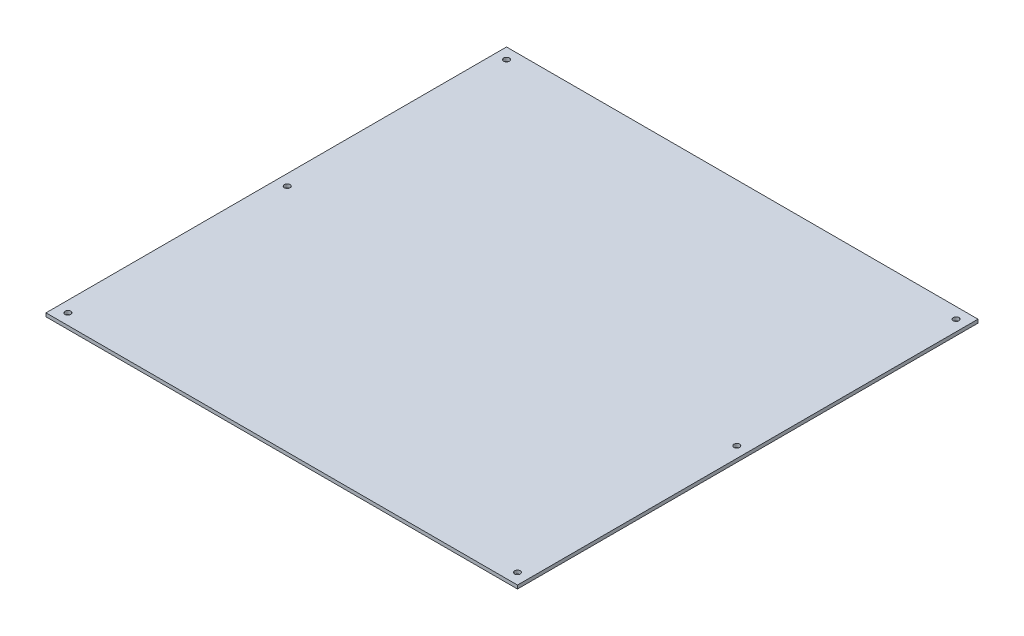
SolidWorks part; units mm, degrees
material "6063-T5"
ref_plane "Front Plane" through (0, 0, 0) normal (0, 0, 1) x (1, 0, 0)
ref_plane "Top Plane" through (0, 0, 0) normal (0, 1, 0) x (1, 0, 0)
ref_plane "Right Plane" through (0, 0, 0) normal (1, 0, 0) x (0, 0, -1)
sketch "Sketch2" plane through (0, 0, 0) normal (0, 1, 0) x (1, 0, 0)
  line L0 (-215, -210) -> (215, -210)
  line L1 (-215, -210) -> (-215, 210)
  line L2 (215, -210) -> (215, 210)
  line L3 (-215, 210) -> (215, 210)
  line L4 (-215, -210) -> (215, 210) construction
  line L5 (215, -210) -> (-215, 210) construction
  line L6 (-205, 200) -> (205, 200) construction
  line L7 (205, 200) -> (205, -200) construction
  line L8 (205, -200) -> (-205, -200) construction
  line L9 (-205, -200) -> (-205, 200) construction
  line L10 (0, 301.643) -> (0, -298.9072) construction
  line L11 (-264.2047, 0) -> (279.6955, 0) construction
  circle A0 centre (-205, 200) radius 2.6
  circle A1 centre (205, 200) radius 2.6
  circle A2 centre (205, -200) radius 2.6
  circle A3 centre (-205, -200) radius 2.6
  circle A4 centre (-205, 0) radius 2.6
  circle A5 centre (205, 0) radius 2.6
  point P1 (0, 0)
  point P14 (0, 200)
  point P15 (205, 0)
  dimension "D3" = 5.2
  dimension "D1" = 430
  dimension "D2" = 420
  dimension "D4" = 410
  dimension "D5" = 400
extrude "Boss-Extrude1" add sketch "Sketch2" along normal mid plane 3.175
ref_axis "Axis1" through (-205, 1.5875, -200) along (0, -1, 0)
ref_axis "Axis3" through (-205, 1.5875, 200) along (0, -1, 0)
ref_axis "Axis4" through (205, 1.5875, 0) along (0, -1, 0)
